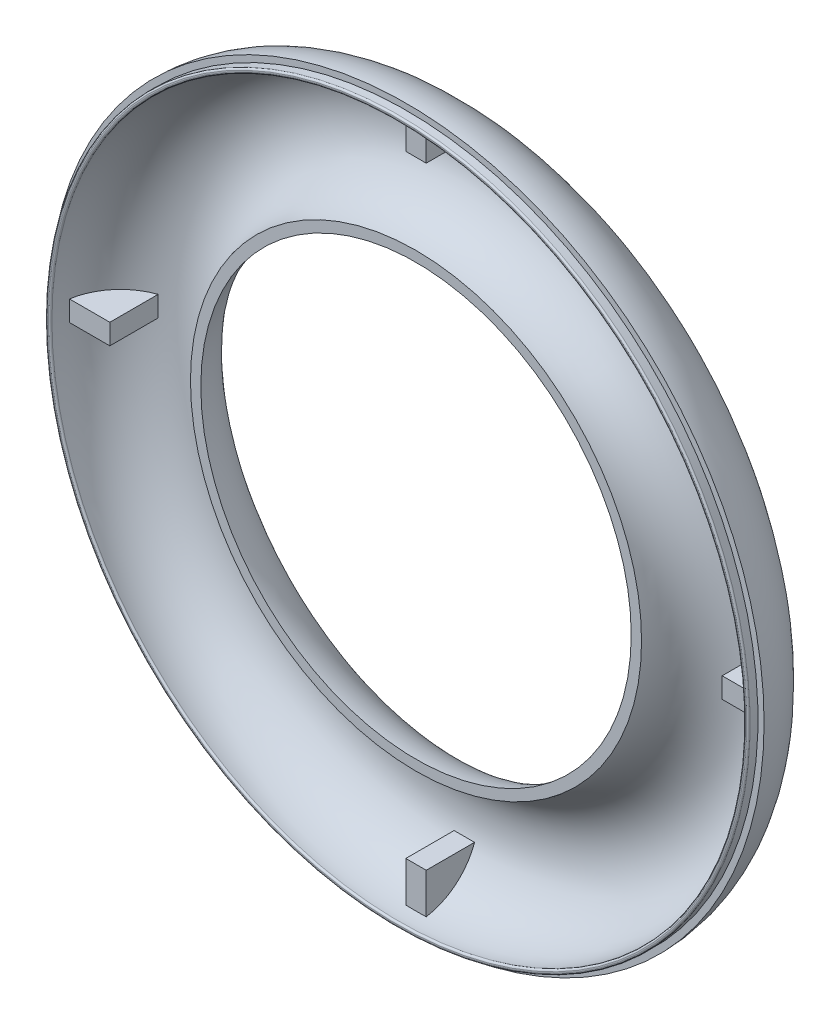
SolidWorks part; units mm, degrees
ref_plane "Front Plane" through (0, 0, 0) normal (0, 0, 1) x (1, 0, 0)
ref_plane "Top Plane" through (0, 0, 0) normal (0, 1, 0) x (1, 0, 0)
ref_plane "Right Plane" through (0, 0, 0) normal (1, 0, 0) x (0, 0, -1)
ref_axis "Polar Axis" through (0, 0, -81.2751) along (0, 0, 1)
ref_axis "Solar Axis" through (-89.4943, 0, 0) along (1, 0, 0)
sketch "Belt Path" plane through (0, 0, 0) normal (0, 0, 1) x (1, 0, 0)
  circle A2 centre (0, 0) radius 42
  dimension "D1" = 84
sketch "Belt Profile" plane through (0, 0, 0) normal (0, 1, 0) x (1, 0, 0)
  line L0 (-52.5, 0) -> (-51.6, 0)
  line L1 (-42, 0) -> (42, 0) construction
  line L2 (-42, 0) -> (42, 0) construction
  line L3 (-42, 9) -> (-42, 0) construction
  line L4 (-51.6, 0) -> (-51.6, -1.4)
  line L5 (-51.6, -1.4) -> (-50.8904, -1.4)
  line L9 (-31.5938, 1.4) -> (-33.1096, 1.4)
  arc A0 (-31.5938, 1.4) -> (-52.5, 0) centre (-42, 0) ccw
  arc A2 (-33.1096, 1.4) -> (-50.8904, -1.4) centre (-42, 0) ccw
  point P0 (-65, 0)
  point P2 (-54, 0)
  point P3 (-65, 0)
  point P9 (-52.568, 3.8008)
  dimension "D1" = 42
  dimension "D2" = 21
  dimension "D3" = 9
  dimension "D4" = 0.9
  dimension "D5" = 1.4
  dimension "D6" = 0.7096
  dimension "D7" = 1.4
sweep "Main Belt" add profiles "Belt Profile" path "Belt Path"
sketch "Ledge Sketch" plane through (0, 0, 0) normal (0, 0, 1) x (1, 0, 0)
  line L0 (-50.9443, 0) -> (-44.9443, 0) construction
  line L1 (-50.9443, -1.5) -> (-44.9443, -1.5)
  line L2 (0, 11.1286) -> (0, -8.5508) construction
  line L3 (-50.9443, -1.5) -> (-50.9443, 1.5)
  line L4 (-50.9443, 1.5) -> (-44.9443, 1.5)
  line L5 (-44.9443, -1.5) -> (-44.9443, 1.5)
  line L6 (1.5, 50.9443) -> (1.5, 44.9443)
  line L7 (-1.5, 50.9443) -> (1.5, 50.9443)
  line L8 (-1.5, 50.9443) -> (-1.5, 44.9443)
  line L9 (-1.5, 44.9443) -> (1.5, 44.9443)
  line L10 (50.9443, -1.5) -> (44.9443, -1.5)
  line L11 (50.9443, 1.5) -> (50.9443, -1.5)
  line L12 (50.9443, 1.5) -> (44.9443, 1.5)
  line L13 (-7.2952, 0) -> (8.7064, 0) construction
  line L14 (44.9443, 1.5) -> (44.9443, -1.5)
  line L15 (-1.5, -50.9443) -> (-1.5, -44.9443)
  line L16 (1.5, -50.9443) -> (-1.5, -50.9443)
  line L17 (1.5, -50.9443) -> (1.5, -44.9443)
  line L18 (1.5, -44.9443) -> (-1.5, -44.9443)
  circle A0 centre (0, 0) radius 50.8904 construction
  circle A1 centre (0, 0) radius 50.8904 construction
  point P11 (-50.8904, 0)
  point P29 (0, 0)
  dimension "D1" = 3
  dimension "D2" = 6
  dimension "D3" = 4
extrude "Ledge" add sketch "Ledge Sketch" against normal up to next from offset 1.4 offset against normal yes
fillet "Lip Fillet" radius 0.25 2 edges at (-51.6, 0, 1.4) (-50.8904, 0, 1.4)
